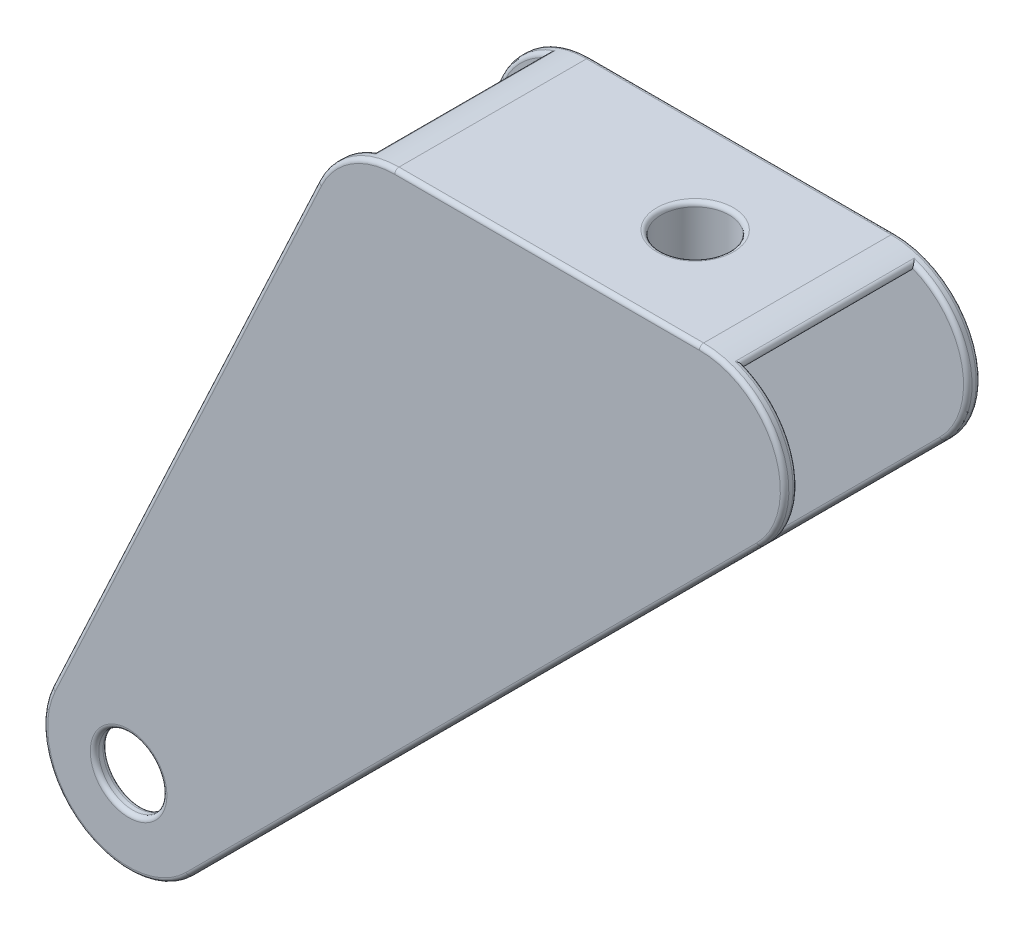
SolidWorks part; units mm, degrees
material "1.4305 (X8CrNiS18-9)"
ref_plane "Płaszczyzna przednia" through (0, 0, 0) normal (0, 0, 1) x (1, 0, 0)
ref_plane "Płaszczyzna górna" through (0, 0, 0) normal (0, 1, 0) x (1, 0, 0)
ref_plane "Płaszczyzna prawa" through (0, 0, 0) normal (1, 0, 0) x (0, 0, -1)
sketch "Szkic1" plane through (0, 0, 0) normal (0, 0, 1) x (1, 0, 0)
  line L0 (7.0711, -7.0711) -> (74.0711, 59.9289)
  line L5 (67, 77) -> (31.2426, 77)
  line L6 (22.1795, 71.2262) -> (-9.0631, 4.2262)
  line L7 (-90.573, 0) -> (129.4295, 0) construction
  line L8 (0, -65.073) -> (0, 87.6034) construction
  arc A0 (-9.0631, 4.2262) -> (7.0711, -7.0711) centre (0, 0) ccw
  arc A1 (31.2426, 77) -> (22.1795, 71.2262) centre (31.2426, 67) ccw
  arc A2 (74.0711, 59.9289) -> (67, 77) centre (67, 67) ccw
  dimension "D1" = 20
  dimension "D4" = 10
  dimension "D2" = 45
  dimension "D3" = 77
  dimension "D5" = 65
extrude "Dodanie-wyciągnięcie1" add sketch "Szkic1" along normal blind 11.5 and the other way blind 11.5
sketch "Szkic3" plane through (0, 0, 0) normal (1, 0, 0) x (0, 0, -1)
  line L0 (11.5, 77) -> (-11.5, 77) construction
  line L1 (-10, -75.5) -> (10, -75.5)
  line L2 (-10, -75.5) -> (-10, 75.5)
  line L3 (-10, 75.5) -> (10, 75.5)
  line L4 (10, -75.5) -> (10, 75.5)
  line L5 (-10, -75.5) -> (10, 75.5) construction
  line L6 (-10, 75.5) -> (10, -75.5) construction
  line L7 (11.5, -7.0711) -> (11.5, 59.9289) construction
  point P0 (0, 0)
  dimension "D1" = 1.5
  dimension "D2" = 1.5
extrude "Wytnij-wyciągnięcie1" cut sketch "Szkic3" against normal through all and the other way through all
sketch "Szkic4" plane through (0, 0, -11.5) normal (0, 0, -1) x (-1, 0, 0)
  circle A0 centre (0, 0) radius 4
  dimension "D1" = 8
extrude "Wytnij-wyciągnięcie2" cut sketch "Szkic4" against normal through all
sketch "Szkic5" plane through (0, 77, 0) normal (0, 1, 0) x (1, 0, 0)
  circle A0 centre (55, 0) radius 4
  dimension "D1" = 8
  dimension "D2" = 55
extrude "Wytnij-wyciągnięcie3" cut sketch "Szkic5" against normal blind 23
fillet "Zaokrąglenie1" radius 0.5 29 edges at (40.5711, 26.4289, 10) (-5.7358, -8.1915, 10) (6.5582, 37.7262, 10) (40.5711, 26.4289, -10) (-5.7358, -8.1915, -10) (6.5582, 37.7262, -10) (40.5711, 26.4289, -11.5) (-5.7358, -8.1915, -11.5) (6.5582, 37.7262, -11.5) (76.2388, 70.8268, -11.5) (76.9336, 68.1504, -10) (72.2678, 75.5, 0) (76.9336, 68.1504, 10) (25.8696, 75.4339, -11.5) (23.7653, 73.64, 10) (25.9748, 75.5, 0) (23.7653, 73.64, -10) (49.1213, 77, -11.5) (51, 77, 0) (6.5582, 37.7262, 11.5) (25.8696, 75.4339, 11.5) (49.1213, 77, 11.5) (76.2388, 70.8268, 11.5) (40.5711, 26.4289, 11.5) (-5.7358, -8.1915, 11.5) (-4, 0, 11.5) (4, 0, 10) (-4, 0, -10) (-4, 0, -11.5)
sketch "Szkic6" plane through (0, 75.5, 0) normal (0, -1, 0) x (1, 0, 0)
  circle A0 centre (55, 0) radius 5
  circle A1 centre (55, 0) radius 4
  dimension "D1" = 10
  dimension "D2" = 8
extrude "Dodanie-wyciągnięcie2" add sketch "Szkic6" along normal blind 9
